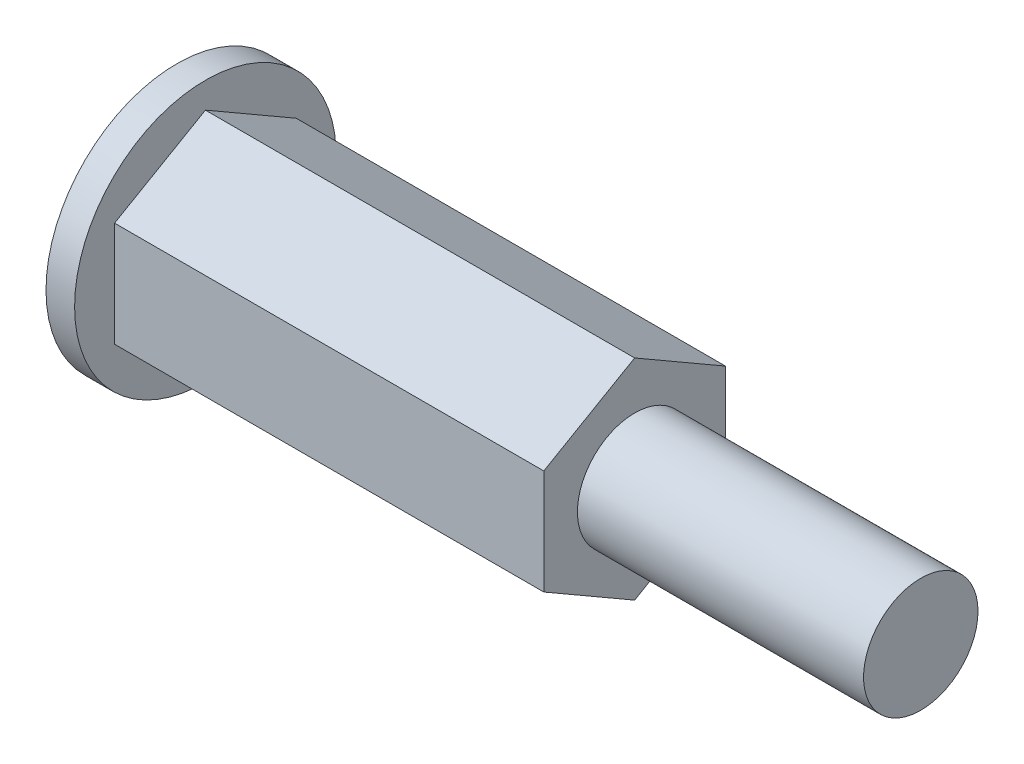
SolidWorks part; units mm, degrees
ref_plane "Front Plane" through (0, 0, 0) normal (1, 0, 0) x (0, 1, 0)
ref_plane "Top Plane" through (0, 0, 0) normal (0, 0, 1) x (0, 1, 0)
ref_plane "Right Plane" through (0, 0, 0) normal (0, 1, 0) x (-1, 0, 0)
sketch "Sketch1" plane through (0, 0, 0) normal (1, 0, 0) x (0, 1, 0)
  circle A0 centre (0, 0) radius 3.999
  dimension "D1" = 7.998
extrude "Boss-Extrude1" add sketch "Sketch1" along normal blind 50
sketch "Sketch2" plane through (0, 0, 0) normal (-1, 0, 0) x (0, -1, 0)
  circle A0 centre (0, 0) radius 9.141
  dimension "D1" = 18.282
extrude "Boss-Extrude2" add sketch "Sketch2" along normal blind 2
sketch "Sketch3" plane through (0, 0, 0) normal (1, 0, 0) x (0, 1, 0)
  line L1 (3.665, 6.348) -> (-3.665, 6.348)
  line L2 (-3.665, 6.348) -> (-7.33, 0)
  line L3 (-7.33, 0) -> (-3.665, -6.348)
  line L4 (-3.665, -6.348) -> (3.665, -6.348)
  line L5 (3.665, -6.348) -> (7.33, 0)
  line L6 (7.33, 0) -> (3.665, 6.348)
  circle A0 centre (0, 0) radius 6.348 construction
  dimension "D2" = 12.6959
  dimension "D1" = 7.33
extrude "Boss-Extrude3" add sketch "Sketch3" along normal blind 30
